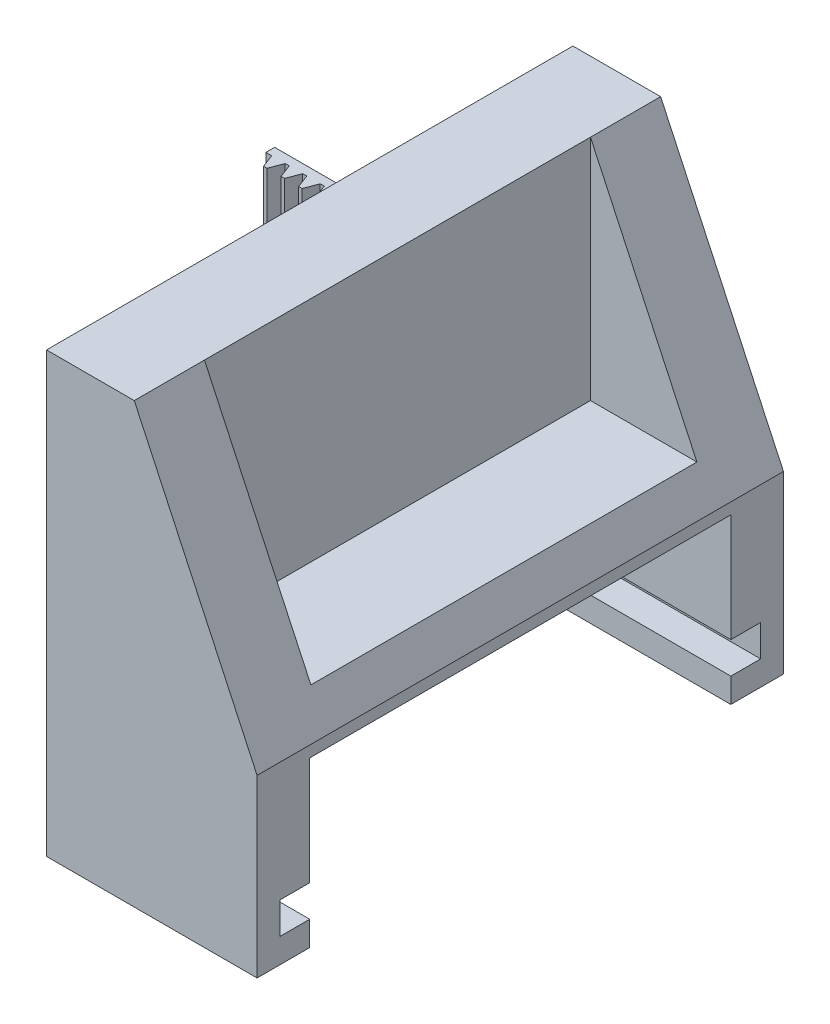
SolidWorks part; units mm, degrees
ref_plane "Front Plane" through (0, 0, 0) normal (0, 0, 1) x (1, 0, 0)
ref_plane "Top Plane" through (0, 0, 0) normal (0, 1, 0) x (1, 0, 0)
ref_plane "Right Plane" through (0, 0, 0) normal (1, 0, 0) x (0, 0, -1)
sketch "Sketch1" plane through (0, 0, 0) normal (0, 0, 1) x (1, 0, 0)
  line L0 (0, 0) -> (0, -25)
  line L1 (0, -25) -> (12, -25)
  line L2 (12, -25) -> (12, -15)
  line L3 (12, -15) -> (5, 0)
  line L4 (5, 0) -> (0, 0)
  dimension "D1" = 25
  dimension "D2" = 12
  dimension "D3" = 10
  dimension "D4" = 5
extrude "Boss-Extrude1" add sketch "Sketch1" against normal blind 30
sketch "Sketch4" plane through (0, 0, 0) normal (-1, 0, 0) x (0, 0, 1)
  line L0 (-30, 0) -> (-30, -25) construction
  line L1 (-27, -15.6386) -> (-3, -15.6386)
  line L2 (-27, -15.6386) -> (-27, -29.6386)
  line L3 (-27, -29.6386) -> (-3, -29.6386)
  line L4 (-3, -15.6386) -> (-3, -29.6386)
  point P4 (-27, -22.6386)
  dimension "D1" = 24
  dimension "D2" = 14
  dimension "D3" = 3
extrude "Cut-Extrude2" cut sketch "Sketch4" against normal blind 25 contours L2 L1 L4 L3
sketch "Sketch5" plane through (0, 0, 0) normal (-1, 0, 0) x (0, 0, 1)
  line L0 (-3, -15.6386) -> (-3, -25) construction
  line L1 (-3, -21.8) -> (-1.3, -21.8)
  line L2 (-3, -21.8) -> (-3, -23.6)
  line L3 (-3, -23.6) -> (-1.3, -23.6)
  line L4 (-1.3, -21.8) -> (-1.3, -23.6)
  line L5 (-3, -25) -> (0, -25) construction
  dimension "D1" = 1.8
  dimension "D2" = 1.7
  dimension "D3" = 1.4
extrude "Cut-Extrude3" cut sketch "Sketch5" against normal blind 15
ref_plane "Plane1" through (0, 0, -15) normal (0, 0, 1) x (1, 0, 0)
mirror "Mirror1" about plane through (0, 0, -15) normal (0, 0, 1) of "Cut-Extrude3"
sketch "Sketch6" plane through (0, 0, -15) normal (0, 0, 1) x (1, 0, 0)
  line L0 (5, 0) -> (5, -13)
  line L1 (5, -13) -> (11.0667, -13)
  line L2 (12, -15) -> (5, 0) construction
  line L3 (11.0667, -13) -> (5, 0)
  dimension "D1" = 13
extrude "Cut-Extrude4" cut sketch "Sketch6" against normal mid plane 22
ref_plane "Plane2" through (0, -15, 0) normal (0, 1, 0) x (1, 0, 0)
sketch "Sketch7" plane through (0, -15, 0) normal (0, 1, 0) x (1, 0, 0)
  line L0 (0, 27.5) -> (-14.5, 27.5)
  line L1 (0, 30) -> (0, 0) construction
  line L2 (-14.5, 27.5) -> (-14.5, 27)
  line L3 (0, 27.5) -> (0, 27)
  line L4 (0, 27) -> (-0.4, 27)
  line L5 (-0.8812, 26.251) -> (-1.1644, 27)
  line L6 (-0.4, 27) -> (-0.6812, 26.251)
  line L7 (-0.6812, 26.251) -> (-0.8812, 26.251)
  line L8 (-1.8812, 26.251) -> (-2.1644, 27)
  line L9 (-1.6812, 26.251) -> (-1.8812, 26.251)
  line L10 (-1.4, 27) -> (-1.6812, 26.251)
  line L11 (-2.8812, 26.251) -> (-3.1644, 27)
  line L12 (-2.6812, 26.251) -> (-2.8812, 26.251)
  line L13 (-2.4, 27) -> (-2.6812, 26.251)
  line L14 (-3.8812, 26.251) -> (-4.1644, 27)
  line L15 (-3.6812, 26.251) -> (-3.8812, 26.251)
  line L16 (-3.4, 27) -> (-3.6812, 26.251)
  line L17 (-4.8812, 26.251) -> (-5.1644, 27)
  line L18 (-4.6812, 26.251) -> (-4.8812, 26.251)
  line L19 (-4.4, 27) -> (-4.6812, 26.251)
  line L20 (-5.8812, 26.251) -> (-6.1644, 27)
  line L21 (-5.6812, 26.251) -> (-5.8812, 26.251)
  line L22 (-5.4, 27) -> (-5.6812, 26.251)
  line L23 (-6.8812, 26.251) -> (-7.1644, 27)
  line L24 (-6.6812, 26.251) -> (-6.8812, 26.251)
  line L25 (-6.4, 27) -> (-6.6812, 26.251)
  line L26 (-7.8812, 26.251) -> (-8.1644, 27)
  line L27 (-7.6812, 26.251) -> (-7.8812, 26.251)
  line L28 (-7.4, 27) -> (-7.6812, 26.251)
  line L29 (-8.8812, 26.251) -> (-9.1644, 27)
  line L30 (-8.6812, 26.251) -> (-8.8812, 26.251)
  line L31 (-8.4, 27) -> (-8.6812, 26.251)
  line L32 (-9.8812, 26.251) -> (-10.1644, 27)
  line L33 (-9.6812, 26.251) -> (-9.8812, 26.251)
  line L34 (-9.4, 27) -> (-9.6812, 26.251)
  line L35 (-10.8812, 26.251) -> (-11.1644, 27)
  line L36 (-10.6812, 26.251) -> (-10.8812, 26.251)
  line L37 (-10.4, 27) -> (-10.6812, 26.251)
  line L38 (-11.8812, 26.251) -> (-12.1644, 27)
  line L39 (-11.6812, 26.251) -> (-11.8812, 26.251)
  line L40 (-11.4, 27) -> (-11.6812, 26.251)
  line L41 (-12.8812, 26.251) -> (-13.1644, 27)
  line L42 (-12.6812, 26.251) -> (-12.8812, 26.251)
  line L43 (-12.4, 27) -> (-12.6812, 26.251)
  line L44 (-13.8812, 26.251) -> (-14.1644, 27)
  line L45 (-13.6812, 26.251) -> (-13.8812, 26.251)
  line L46 (-13.4, 27) -> (-13.6812, 26.251)
  line L47 (-0.8812, 26.251) -> (-1.8812, 26.251) construction
  line L48 (-1.1644, 27) -> (-1.4, 27)
  line L49 (-2.1644, 27) -> (-2.4, 27)
  line L50 (-3.1644, 27) -> (-3.4, 27)
  line L51 (-4.1644, 27) -> (-4.4, 27)
  line L52 (-5.1644, 27) -> (-5.4, 27)
  line L53 (-6.1644, 27) -> (-6.4, 27)
  line L54 (-7.1644, 27) -> (-7.4, 27)
  line L55 (-8.1644, 27) -> (-8.4, 27)
  line L56 (-9.1644, 27) -> (-9.4, 27)
  line L57 (-10.1644, 27) -> (-10.4, 27)
  line L58 (-11.1644, 27) -> (-11.4, 27)
  line L59 (-12.1644, 27) -> (-12.4, 27)
  line L60 (-13.1644, 27) -> (-13.4, 27)
  line L61 (-14.1644, 27) -> (-14.5, 27)
  line L62 (-14.575, 15) -> (14.575, 15) construction
  dimension "D1" = 0.8
  dimension "D4" = 0.2
  dimension "D2" = 14.5
  dimension "D3" = 0.5
  dimension "D5" = 1
  dimension "D6" = 0.4
  dimension "D7" = 12.5
  dimension "D8" = 14
extrude "Boss-Extrude2" add sketch "Sketch7" along normal blind 4
